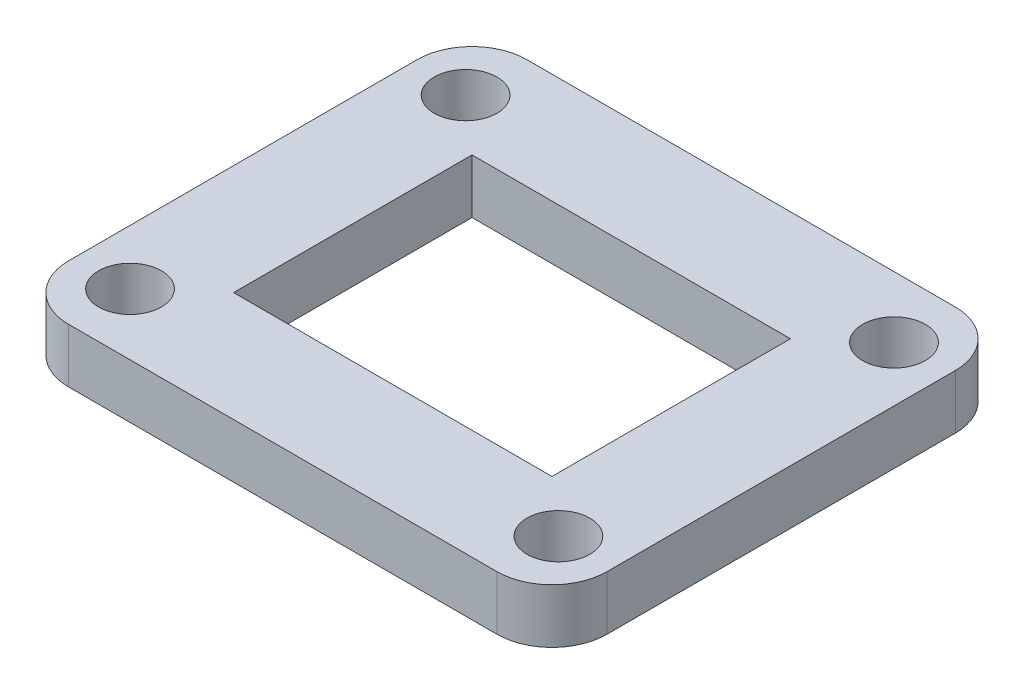
SolidWorks part; units mm, degrees
ref_plane "Front Plane" through (0, 0, 0) normal (0, 0, 1) x (1, 0, 0)
ref_plane "Top Plane" through (0, 0, 0) normal (0, 1, 0) x (1, 0, 0)
ref_plane "Right Plane" through (0, 0, 0) normal (1, 0, 0) x (0, 0, -1)
sketch "Sketch1" plane through (0, 0, 0) normal (0, 1, 0) x (1, 0, 0)
  line L6 (-15, -11.75) -> (15, -11.75) construction
  line L11 (-15, -11.75) -> (-15, 11.75) construction
  line L16 (-15, 11.75) -> (15, 11.75) construction
  line L17 (15, -11.75) -> (15, 11.75) construction
  line L18 (-15, -11.75) -> (15, 11.75) construction
  line L19 (-15, 11.75) -> (15, -11.75) construction
  line L20 (-15, -16.05) -> (15, -16.05)
  line L21 (-18.85, -12.2) -> (-18.85, 12.2)
  line L22 (-15, 16.05) -> (15, 16.05)
  line L23 (18.85, -12.2) -> (18.85, 12.2)
  line L24 (-18.85, -16.05) -> (18.85, 16.05) construction
  line L25 (-18.85, 16.05) -> (18.85, -16.05) construction
  line L34 (-11.15, -8.35) -> (11.15, -8.35)
  line L35 (-11.15, -8.35) -> (-11.15, 8.35)
  line L36 (-11.15, 8.35) -> (11.15, 8.35)
  line L37 (11.15, -8.35) -> (11.15, 8.35)
  line L38 (-11.15, -8.35) -> (11.15, 8.35) construction
  line L39 (-11.15, 8.35) -> (11.15, -8.35) construction
  arc A12 (-18.85, -12.2) -> (-15, -16.05) centre (-15, -12.2) ccw
  arc A13 (18.85, -12.2) -> (15, -16.05) centre (15, -12.2) cw
  arc A14 (18.85, 12.2) -> (15, 16.05) centre (15, 12.2) ccw
  arc A15 (-18.85, 12.2) -> (-15, 16.05) centre (-15, 12.2) cw
  circle A16 centre (-15, 11.75) radius 2.2
  circle A17 centre (15, 11.75) radius 2.2
  circle A18 centre (-15, -11.75) radius 2.2
  circle A19 centre (15, -11.75) radius 2.2
  point P0 (0, 0)
  point P3 (0, 0)
  point P6 (0, 0)
  dimension "D3" = 37.7
  dimension "D6" = 4.4
  dimension "D5" = 3.85
  dimension "D1" = 23.5
  dimension "D2" = 30
  dimension "D4" = 32.1
  dimension "D7" = 7.7
  dimension "D8" = 7.7
extrude "Boss-Extrude1" add sketch "Sketch1" along normal blind 3.8
